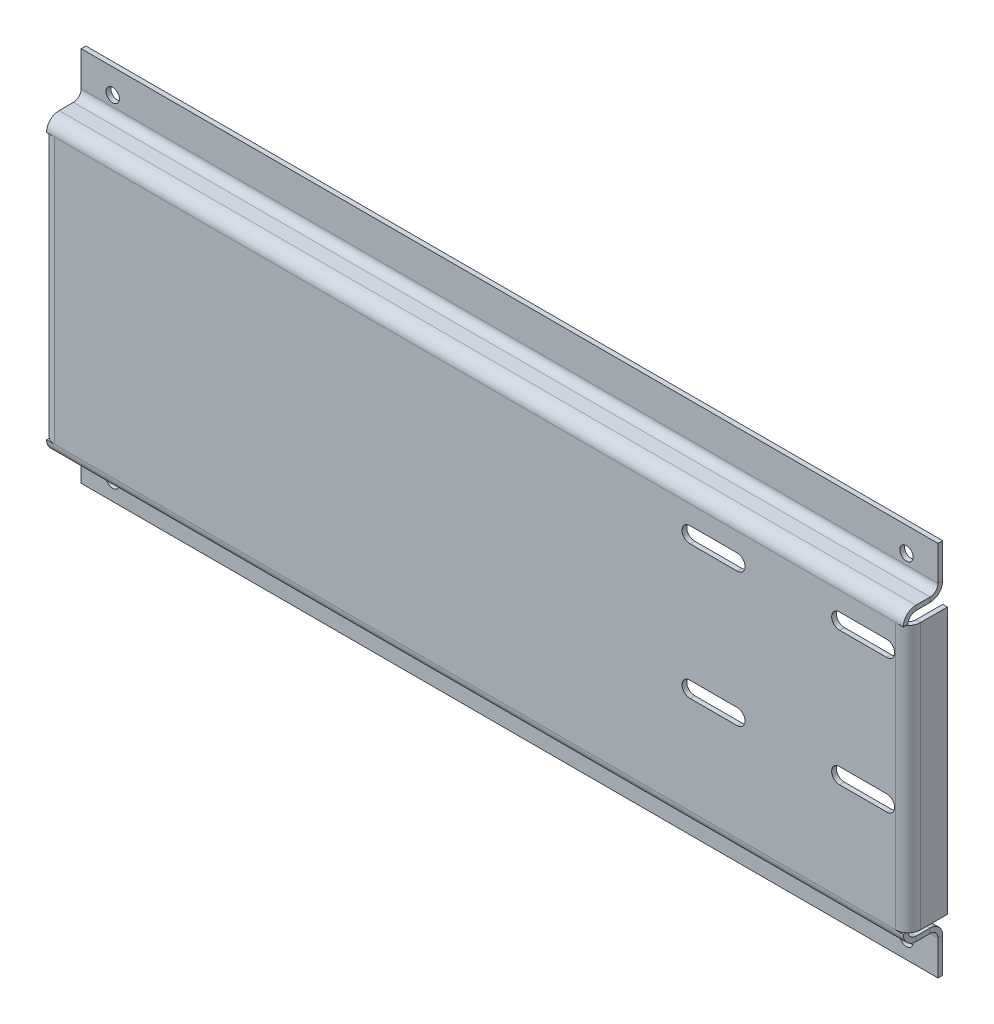
SolidWorks part; units mm, degrees
note: The reader was unsure of these and kept them because the rebuilt part matched: flange length of "Edge-Flange1", "Edge-Flange2", "Edge-Flange3", "Edge-Flange4", "Edge-Flange5", "Edge-Flange6".
material "ASTM A36 Steel"
ref_plane "Front Plane" through (0, 0, 0) normal (0, 0, 1) x (1, 0, 0)
ref_plane "Top Plane" through (0, 0, 0) normal (0, 1, 0) x (1, 0, 0)
ref_plane "Right Plane" through (0, 0, 0) normal (1, 0, 0) x (0, 0, -1)
sketch "Sketch1" plane through (0, 0, 0) normal (0, 0, 1) x (1, 0, 0)
  line L0 (152.5372, 9.9755) -> (122.5372, 9.9755) construction
  line L1 (163.0372, 34.9755) -> (-380.9628, 34.9755)
  line L2 (163.0372, 34.9755) -> (163.0372, -150.0245)
  line L3 (163.0372, -150.0245) -> (-380.9628, -150.0245)
  line L4 (-380.9628, 34.9755) -> (-380.9628, -150.0245)
  line L5 (152.5372, 4.9755) -> (122.5372, 4.9755)
  line L6 (152.5372, 14.9755) -> (122.5372, 14.9755)
  line L7 (57.5372, 9.9755) -> (27.5372, 9.9755) construction
  line L8 (57.5372, 4.9755) -> (27.5372, 4.9755)
  line L9 (57.5372, 14.9755) -> (27.5372, 14.9755)
  line L10 (152.5372, -75.0245) -> (122.5372, -75.0245) construction
  line L11 (152.5372, -80.0245) -> (122.5372, -80.0245)
  line L12 (152.5372, -70.0245) -> (122.5372, -70.0245)
  line L13 (57.5372, -75.0245) -> (27.5372, -75.0245) construction
  line L14 (57.5372, -80.0245) -> (27.5372, -80.0245)
  line L15 (57.5372, -70.0245) -> (27.5372, -70.0245)
  arc A0 (152.5372, 4.9755) -> (152.5372, 14.9755) centre (152.5372, 9.9755) ccw
  arc A1 (122.5372, 14.9755) -> (122.5372, 4.9755) centre (122.5372, 9.9755) ccw
  arc A2 (57.5372, 4.9755) -> (57.5372, 14.9755) centre (57.5372, 9.9755) ccw
  arc A3 (27.5372, 14.9755) -> (27.5372, 4.9755) centre (27.5372, 9.9755) ccw
  arc A4 (152.5372, -80.0245) -> (152.5372, -70.0245) centre (152.5372, -75.0245) ccw
  arc A5 (122.5372, -70.0245) -> (122.5372, -80.0245) centre (122.5372, -75.0245) ccw
  arc A6 (57.5372, -80.0245) -> (57.5372, -70.0245) centre (57.5372, -75.0245) ccw
  arc A7 (27.5372, -70.0245) -> (27.5372, -80.0245) centre (27.5372, -75.0245) ccw
  point P6 (137.5372, 9.9755)
  point P11 (42.5372, 9.9755)
  point P18 (137.5372, -75.0245)
  point P25 (42.5372, -75.0245)
  point P33 (157.5372, 9.9755)
  dimension "D8" = 5.5
  dimension "D1" = 544
  dimension "D2" = 185
  dimension "D3" = 25
  dimension "D4" = 85
  dimension "D5" = 25.5
  dimension "D6" = 10
  dimension "D7" = 30
  dimension "D9" = 30
  dimension "D10" = 25.5
  dimension "D11" = 95
  dimension "D12" = 10
  dimension "D13" = 30
  dimension "D14" = 95
  dimension "D15" = 34.9755
  dimension "D16" = 30
base flange "Base-Flange1" sketch "Sketch1" thickness 3 reverse thickness direction no parameters "D1"=0.7366
edge flange "Edge-Flange1" sketch "Sketch10" flange angle 90 flange length 25 flange position material inside bend radius 5 thickness 3 relief rectangular parameters "D6"=10
sketch "Sketch10" plane through (0, 34.9755, -3) normal (0, -1, 0) x (-1, 0, 0)
  line L2 (-163.0372, 0) -> (-163.0372, 22)
  line L3 (-163.0372, 22) -> (380.9628, 22)
  line L4 (380.9628, 22) -> (380.9628, 0)
  line L6 (380.9628, 0) -> (-163.0372, 0) construction
  line L7 (380.9628, 0) -> (-163.0372, 0)
bend "EdgeBend1" bend radius 5 bend angle 90 parameters "D5"=1
edge flange "Edge-Flange2" sketch "Sketch13" flange angle 90 flange length 25 flange position material inside bend radius 5 thickness 3 relief rectangular parameters "D6"=10
sketch "Sketch13" plane through (0, -150.0245, -3) normal (0, 1, 0) x (1, 0, 0)
  line L1 (163.0372, 0) -> (-380.9628, 0) construction
  line L2 (-380.9628, 0) -> (-380.9628, 22)
  line L3 (-380.9628, 22) -> (163.0372, 22)
  line L4 (163.0372, 22) -> (163.0372, 0)
  line L5 (163.0372, 0) -> (-380.9628, 0)
bend "EdgeBend2" bend radius 5 bend angle 90 parameters "D5"=2
edge flange "Edge-Flange3" sketch "Sketch16" flange angle 90 flange length 30 flange position material inside bend radius 5 thickness 3 relief rectangular parameters "D6"=10
sketch "Sketch16" plane through (0, -150.0245, -25) normal (0, 0, 1) x (-1, 0, 0)
  line L1 (380.9628, 0) -> (-163.0372, 0) construction
  line L2 (-163.0372, 0) -> (-163.0372, 27)
  line L3 (-163.0372, 27) -> (380.9628, 27)
  line L4 (380.9628, 27) -> (380.9628, 0)
  line L5 (380.9628, 0) -> (-163.0372, 0)
bend "EdgeBend3" bend radius 5 bend angle 90 parameters "D5"=3
edge flange "Edge-Flange4" sketch "Sketch19" flange angle 90 flange length 30 flange position material inside bend radius 5 thickness 3 relief rectangular parameters "D6"=10
sketch "Sketch19" plane through (0, 34.9755, -25) normal (0, 0, 1) x (1, 0, 0)
  line L1 (163.0372, 0) -> (-380.9628, 0) construction
  line L2 (-380.9628, 0) -> (-380.9628, 27)
  line L3 (-380.9628, 27) -> (163.0372, 27)
  line L4 (163.0372, 27) -> (163.0372, 0)
  line L5 (163.0372, 0) -> (-380.9628, 0)
bend "EdgeBend4" bend radius 5 bend angle 90 parameters "D5"=4
edge flange "Edge-Flange5" sketch "Sketch22" flange angle 90 flange length 25 flange position material outside bend radius 5 thickness 3 relief none parameters "D6"=10
sketch "Sketch22" plane through (163.0372, 0, -3) normal (-1, 0, 0) x (0, 1, 0)
  line L1 (26.9755, 0) -> (-142.0245, 0) construction
  line L2 (-142.0245, 0) -> (-142.0245, 22)
  line L3 (-142.0245, 22) -> (26.9755, 22)
  line L4 (26.9755, 22) -> (26.9755, 0)
  line L5 (26.9755, 0) -> (-142.0245, 0)
bend "EdgeBend5" bend radius 5 bend angle 90 parameters "D5"=5
edge flange "Edge-Flange6" sketch "Sketch25" flange angle 90 flange length 25 flange position material outside bend radius 5 thickness 3 relief none parameters "D6"=10
sketch "Sketch25" plane through (-380.9628, 0, -3) normal (1, 0, 0) x (0, -1, 0)
  line L2 (-26.9755, 0) -> (-26.9755, 22)
  line L3 (-26.9755, 22) -> (142.0245, 22)
  line L4 (142.0245, 22) -> (142.0245, 0)
  line L6 (142.0245, 0) -> (-26.9755, 0) construction
  line L7 (142.0245, 0) -> (-26.9755, 0)
bend "EdgeBend6" bend radius 5 bend angle 90 parameters "D5"=6
sketch "Sketch26" plane through (0, 0, -22) normal (0, 0, 1) x (1, 0, 0)
  circle A0 centre (143.0372, -165.5245) radius 4.25
  circle A1 centre (-360.9628, -165.5245) radius 4.25
  dimension "D2" = 8.5
  dimension "D4" = 8.5
  dimension "D1" = 20
  dimension "D3" = 20
extrude "Cut-Extrude1" cut sketch "Sketch26" against normal blind 10 normal cut yes
sketch "Sketch27" plane through (0, 0, -22) normal (0, 0, 1) x (1, 0, 0)
  line L0 (163.0372, 39.9755) -> (163.0372, 61.9755) construction
  line L1 (-380.9628, 61.9755) -> (-380.9628, 39.9755) construction
  circle A0 centre (143.0372, 46.4755) radius 4.25
  circle A1 centre (-360.9628, 46.4755) radius 4.25
  dimension "D2" = 8.5
  dimension "D4" = 8.5
  dimension "D1" = 20
  dimension "D3" = 20
extrude "Cut-Extrude2" cut sketch "Sketch27" against normal blind 10 normal cut yes
sketch "Bend-Lines1" [suppressed] plane through (0, 0, 0) normal (0, 1, 0) x (1, 0, 0)
sketch "Bounding-Box1" [suppressed] plane through (0, 0, 0) normal (0, 1, 0) x (1, 0, 0)
sheet metal parameters "Sheet-Metal1" thickness 3 parameters "D1"=0.7366
flat pattern "Flat-Pattern1" [suppressed]
sketch "Bend-Lines2" plane through (0, 0, 0) normal (0, 1, 0) x (1, 0, 0)
sketch3d "Bounding-Box2" [suppressed]
  line L0 (253.9628, -152.0245, 0) -> (-148.0372, -152.0245, 0) construction
  line L1 (253.9628, 32.9755, 0) -> (-148.0372, 32.9755, 0) construction
  line L2 (253.9628, -152.0245, 0) -> (253.9628, 32.9755, 0) construction
  line L3 (-148.0372, -152.0245, 0) -> (-148.0372, 32.9755, 0) construction
sheet metal parameters "Sheet-Metal2" thickness 3 parameters "D1"=0.7366
flat pattern "Flat-Pattern1"
sketch "Bend-Lines2" plane through (0, 0, 0) normal (0, 0, 1) x (1, 0, 0)
  line L0 (148.0372, 30.9955) -> (-253.9628, 30.9955) construction
  line L1 (148.0372, 30.9955) -> (-253.9628, 30.9955) construction
sketch3d "Bounding-Box2" [suppressed]
  line L0 (-253.9628, -152.0245, 0) -> (148.0372, -152.0245, 0) construction
  line L1 (-253.9628, 88.0156, 0) -> (148.0372, 88.0156, 0) construction
  line L2 (-253.9628, -152.0245, 0) -> (-253.9628, 88.0156, 0) construction
  line L3 (148.0372, -152.0245, 0) -> (148.0372, 88.0156, 0) construction
bend of the flat pattern "Flatten-<EdgeBend1>1"
sheet metal parameters "Sheet-Metal3" thickness 3 parameters "D1"=0.7366
flat pattern "Flat-Pattern1"
sketch "Bend-Lines2" plane through (0, 0, 0) normal (0, 0, 1) x (1, 0, 0)
  line L0 (148.0372, 30.9955) -> (-253.9628, 30.9955) construction
  line L1 (148.0372, 30.9955) -> (-253.9628, 30.9955) construction
  line L2 (-253.9628, -150.0445) -> (148.0372, -150.0445) construction
  line L3 (-253.9628, -150.0445) -> (148.0372, -150.0445) construction
sketch3d "Bounding-Box2" [suppressed]
  line L0 (-253.9628, -173.0645, 0) -> (148.0372, -173.0645, 0) construction
  line L1 (-253.9628, 54.0156, 0) -> (148.0372, 54.0156, 0) construction
  line L2 (-253.9628, -173.0645, 0) -> (-253.9628, 54.0156, 0) construction
  line L3 (148.0372, -173.0645, 0) -> (148.0372, 54.0156, 0) construction
bend of the flat pattern "Flatten-<EdgeBend1>1"
bend of the flat pattern "Flatten-<EdgeBend2>1"
sheet metal parameters "Sheet-Metal4" thickness 3 parameters "D1"=0.7366
flat pattern "Flat-Pattern1"
sketch "Bend-Lines2" plane through (0, 0, 0) normal (0, 0, 1) x (1, 0, 0)
  line L0 (148.0372, 30.9955) -> (-253.9628, 30.9955) construction
  line L1 (148.0372, 30.9955) -> (-253.9628, 30.9955) construction
  line L2 (-253.9628, -150.0445) -> (148.0372, -150.0445) construction
  line L3 (-253.9628, -150.0445) -> (148.0372, -150.0445) construction
  line L4 (-253.9628, -171.0846) -> (148.0372, -171.0846) construction
  line L5 (-253.9628, -171.0846) -> (148.0372, -171.0846) construction
sketch3d "Bounding-Box2" [suppressed]
  line L0 (-253.9628, -199.1046, 0) -> (148.0372, -199.1046, 0) construction
  line L1 (-253.9628, 54.0156, 0) -> (148.0372, 54.0156, 0) construction
  line L2 (-253.9628, -199.1046, 0) -> (-253.9628, 54.0156, 0) construction
  line L3 (148.0372, -199.1046, 0) -> (148.0372, 54.0156, 0) construction
bend of the flat pattern "Flatten-<EdgeBend1>1"
bend of the flat pattern "Flatten-<EdgeBend2>1"
bend of the flat pattern "Flatten-<EdgeBend3>1"
sheet metal parameters "Sheet-Metal5" thickness 3 parameters "D1"=0.7366
flat pattern "Flat-Pattern1"
sketch "Bend-Lines2" plane through (0, 0, 0) normal (0, 0, 1) x (1, 0, 0)
  line L0 (148.0372, 30.9955) -> (-253.9628, 30.9955) construction
  line L1 (148.0372, 30.9955) -> (-253.9628, 30.9955) construction
  line L2 (-253.9628, -150.0445) -> (148.0372, -150.0445) construction
  line L3 (-253.9628, -150.0445) -> (148.0372, -150.0445) construction
  line L4 (-253.9628, -171.0846) -> (148.0372, -171.0846) construction
  line L5 (-253.9628, -171.0846) -> (148.0372, -171.0846) construction
  line L6 (148.0372, 52.0356) -> (-253.9628, 52.0356) construction
  line L7 (148.0372, 52.0356) -> (-253.9628, 52.0356) construction
sketch3d "Bounding-Box2" [suppressed]
  line L0 (-253.9628, -199.1046, 0) -> (148.0372, -199.1046, 0) construction
  line L1 (-253.9628, 80.0556, 0) -> (148.0372, 80.0556, 0) construction
  line L2 (-253.9628, -199.1046, 0) -> (-253.9628, 80.0556, 0) construction
  line L3 (148.0372, -199.1046, 0) -> (148.0372, 80.0556, 0) construction
bend of the flat pattern "Flatten-<EdgeBend1>1"
bend of the flat pattern "Flatten-<EdgeBend2>1"
bend of the flat pattern "Flatten-<EdgeBend3>1"
bend of the flat pattern "Flatten-<EdgeBend4>1"
sheet metal parameters "Sheet-Metal6" thickness 3 parameters "D1"=0.7366
flat pattern "Flat-Pattern1"
sketch "Bend-Lines2" plane through (0, 0, 0) normal (0, 0, 1) x (1, 0, 0)
  line L0 (148.0372, 30.9955) -> (-253.9628, 30.9955) construction
  line L1 (148.0372, 30.9955) -> (-253.9628, 30.9955) construction
  line L2 (-253.9628, -150.0445) -> (148.0372, -150.0445) construction
  line L3 (-253.9628, -150.0445) -> (148.0372, -150.0445) construction
  line L4 (-253.9628, -171.0846) -> (148.0372, -171.0846) construction
  line L5 (-253.9628, -171.0846) -> (148.0372, -171.0846) construction
  line L6 (148.0372, 52.0356) -> (-253.9628, 52.0356) construction
  line L7 (148.0372, 52.0356) -> (-253.9628, 52.0356) construction
  line L8 (146.0573, -148.2879) -> (146.0573, 29.2389) construction
  line L9 (146.0573, -148.2879) -> (146.0573, 29.2389) construction
sketch3d "Bounding-Box2" [suppressed]
  line L0 (-253.9628, -199.1046, 0) -> (169.0773, -199.1046, 0) construction
  line L1 (-253.9628, 80.0556, 0) -> (169.0773, 80.0556, 0) construction
  line L2 (-253.9628, -199.1046, 0) -> (-253.9628, 80.0556, 0) construction
  line L3 (169.0773, -199.1046, 0) -> (169.0773, 80.0556, 0) construction
bend of the flat pattern "Flatten-<EdgeBend1>1"
bend of the flat pattern "Flatten-<EdgeBend2>1"
bend of the flat pattern "Flatten-<EdgeBend3>1"
bend of the flat pattern "Flatten-<EdgeBend4>1"
bend of the flat pattern "Flatten-<EdgeBend5>1"
sheet metal parameters "Sheet-Metal7" thickness 3 parameters "D1"=0.7366
flat pattern "Flat-Pattern1"
sketch "Bend-Lines2" plane through (0, 0, 0) normal (0, 0, 1) x (1, 0, 0)
  line L0 (148.0372, 30.9955) -> (-253.9628, 30.9955) construction
  line L1 (148.0372, 30.9955) -> (-253.9628, 30.9955) construction
  line L2 (-253.9628, -150.0445) -> (148.0372, -150.0445) construction
  line L3 (-253.9628, -150.0445) -> (148.0372, -150.0445) construction
  line L4 (-253.9628, -171.0846) -> (148.0372, -171.0846) construction
  line L5 (-253.9628, -171.0846) -> (148.0372, -171.0846) construction
  line L6 (148.0372, 52.0356) -> (-253.9628, 52.0356) construction
  line L7 (148.0372, 52.0356) -> (-253.9628, 52.0356) construction
  line L8 (146.0573, -148.2879) -> (146.0573, 29.2389) construction
  line L9 (146.0573, -148.2879) -> (146.0573, 29.2389) construction
  line L10 (-251.9828, 29.2389) -> (-251.9828, -148.2879) construction
  line L11 (-251.9828, 29.2389) -> (-251.9828, -148.2879) construction
sketch3d "Bounding-Box2" [suppressed]
  line L0 (-275.0028, -199.1046, 0) -> (169.0773, -199.1046, 0) construction
  line L1 (-275.0028, 80.0556, 0) -> (169.0773, 80.0556, 0) construction
  line L2 (-275.0028, -199.1046, 0) -> (-275.0028, 80.0556, 0) construction
  line L3 (169.0773, -199.1046, 0) -> (169.0773, 80.0556, 0) construction
bend of the flat pattern "Flatten-<EdgeBend1>1"
bend of the flat pattern "Flatten-<EdgeBend2>1"
bend of the flat pattern "Flatten-<EdgeBend3>1"
bend of the flat pattern "Flatten-<EdgeBend4>1"
bend of the flat pattern "Flatten-<EdgeBend5>1"
bend of the flat pattern "Flatten-<EdgeBend6>1"
sheet metal parameters "Sheet-Metal8" thickness 3 parameters "D1"=0.7366
flat pattern "Flat-Pattern1"
sketch "Bend-Lines2" plane through (0, 0, 0) normal (0, 0, 1) x (1, 0, 0)
  line L0 (163.0372, 12.0806) -> (-380.9628, 12.0806) construction
  line L1 (163.0372, 12.0806) -> (-380.9628, 12.0806) construction
  line L2 (-380.9628, -167.1296) -> (163.0372, -167.1296) construction
  line L3 (-380.9628, -167.1296) -> (163.0372, -167.1296) construction
  line L4 (-380.9628, -186.3398) -> (-362.7759, -186.3398) construction
  line L5 (-380.9628, -186.3398) -> (-362.7759, -186.3398) construction
  line L6 (163.0372, 31.2908) -> (-380.9628, 31.2908) construction
  line L7 (163.0372, 31.2908) -> (-380.9628, 31.2908) construction
  line L8 (163.1423, -162.0245) -> (163.1423, 6.9755) construction
  line L9 (163.1423, -162.0245) -> (163.1423, 6.9755) construction
  line L10 (-381.0678, 6.9755) -> (-381.0678, -162.0245) construction
  line L11 (-381.0678, 6.9755) -> (-381.0678, -162.0245) construction
  line L12 (-359.1477, -186.3398) -> (141.2241, -186.3398) construction
  line L13 (144.8523, -186.3398) -> (163.0372, -186.3398) construction
sketch3d "Bounding-Box2" [suppressed]
  line L0 (-403.1729, -213.4448, 0) -> (185.2474, -213.4448, 0) construction
  line L1 (-403.1729, 58.3959, 0) -> (185.2474, 58.3959, 0) construction
  line L2 (-403.1729, -213.4448, 0) -> (-403.1729, 58.3959, 0) construction
  line L3 (185.2474, -213.4448, 0) -> (185.2474, 58.3959, 0) construction
bend of the flat pattern "Flatten-<EdgeBend1>1"
bend of the flat pattern "Flatten-<EdgeBend2>1"
bend of the flat pattern "Flatten-<EdgeBend3>1"
bend of the flat pattern "Flatten-<EdgeBend4>1"
bend of the flat pattern "Flatten-<EdgeBend5>1"
bend of the flat pattern "Flatten-<EdgeBend6>1"
sheet metal parameters "Sheet-Metal9" thickness 3 parameters "D1"=0.7366
flat pattern "Flat-Pattern1"
sketch "Bend-Lines2" plane through (0, 0, 0) normal (0, 0, 1) x (1, 0, 0)
  line L0 (163.0372, 32.0806) -> (-380.9628, 32.0806) construction
  line L1 (163.0372, 32.0806) -> (-380.9628, 32.0806) construction
  line L2 (-380.9628, -147.1296) -> (163.0372, -147.1296) construction
  line L3 (-380.9628, -147.1296) -> (163.0372, -147.1296) construction
  line L4 (-380.9628, -166.3398) -> (163.0372, -166.3398) construction
  line L5 (-380.9628, -166.3398) -> (163.0372, -166.3398) construction
  line L6 (163.0372, 51.2908) -> (-380.9628, 51.2908) construction
  line L7 (163.0372, 51.2908) -> (-380.9628, 51.2908) construction
  line L8 (163.1423, -142.0245) -> (163.1423, 26.9755) construction
  line L9 (163.1423, -142.0245) -> (163.1423, 26.9755) construction
  line L10 (-381.0678, 26.9755) -> (-381.0678, -142.0245) construction
  line L11 (-381.0678, 26.9755) -> (-381.0678, -142.0245) construction
sketch3d "Bounding-Box2" [suppressed]
  line L0 (-403.1729, -193.4448, 0) -> (185.2474, -193.4448, 0) construction
  line L1 (-403.1729, 78.3959, 0) -> (185.2474, 78.3959, 0) construction
  line L2 (-403.1729, -193.4448, 0) -> (-403.1729, 78.3959, 0) construction
  line L3 (185.2474, -193.4448, 0) -> (185.2474, 78.3959, 0) construction
bend of the flat pattern "Flatten-<EdgeBend1>1"
bend of the flat pattern "Flatten-<EdgeBend2>1"
bend of the flat pattern "Flatten-<EdgeBend3>1"
bend of the flat pattern "Flatten-<EdgeBend4>1"
bend of the flat pattern "Flatten-<EdgeBend5>1"
bend of the flat pattern "Flatten-<EdgeBend6>1"
